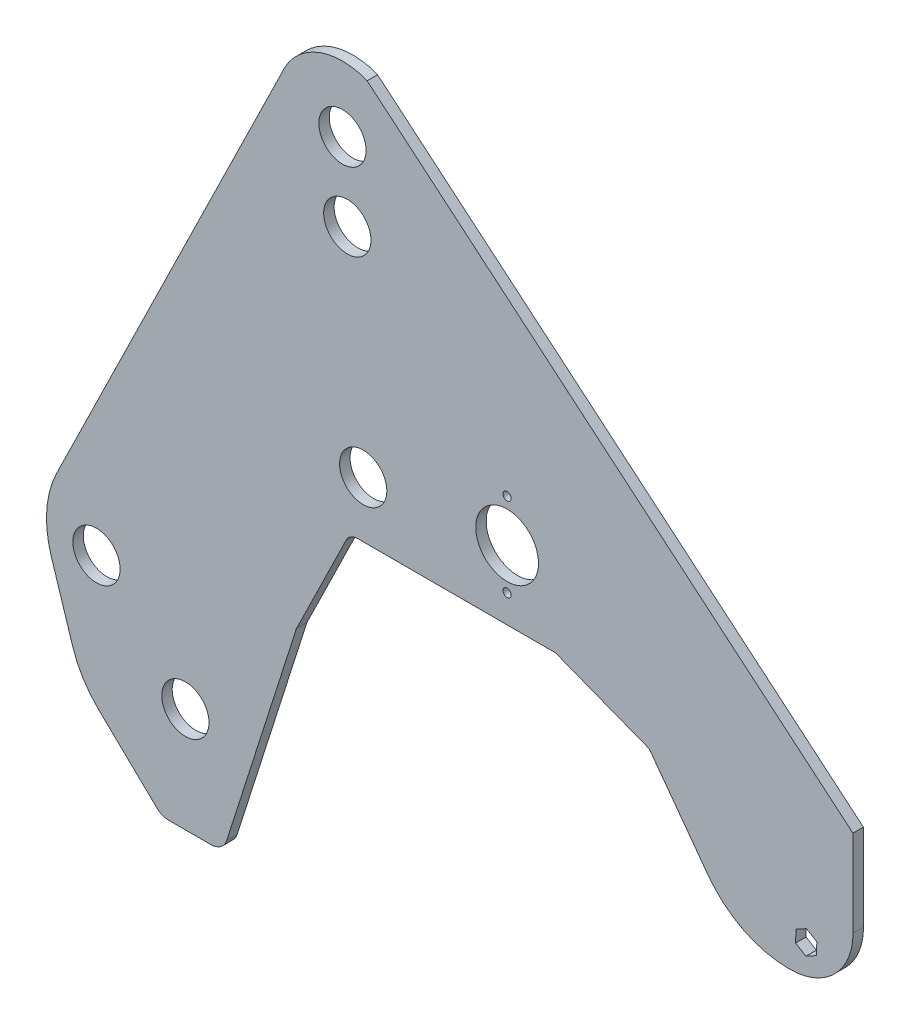
SolidWorks part; units mm, degrees
other "Markup1"
sketch "Sketch1" plane through (-441.7893, 331.8239, 6.35) normal (-0.0431, 0.0102, 0.999) x (0.9985, 0.0354, 0.0427)
ref_plane "Front Plane" through (0, 0, 0) normal (0, 0, 1) x (1, 0, 0)
ref_plane "Top Plane" through (0, 0, 0) normal (0, 1, 0) x (1, 0, 0)
ref_plane "Right Plane" through (0, 0, 0) normal (1, 0, 0) x (0, 0, -1)
sketch "Model" plane through (0, 0, 0) normal (0, 0, 1) x (1, 0, 0)
  line L0 (75.9485, 40.4103) -> (75.882, 92.9412)
  line L1 (-224.8827, 97.4651) -> (-104.7249, 97.4651)
  line L2 (-261.9342, 31.5683) -> (-231.7249, 93.1989)
  line L3 (-304.235, -100.9045) -> (-261.9342, 31.5683)
  line L4 (-271.0052, 318.922) -> (-407.4479, 40.5627)
  line L5 (-410.7965, -4.7638) -> (-397.7579, -45.7118)
  line L6 (-104.7249, 97.4651) -> (-47.7354, 75.4359)
  line L7 (-381.9218, -71.1596) -> (-346.5817, -105.1379)
  line L8 (-47.7354, 75.4359) -> (-12.1905, 27.105)
  line L10 (36.9184, 2.262) -> (37.8485, 2.262)
  line L11 (75.882, 92.9412) -> (-219.0215, 341.0133)
  line L12 (-339.5399, -107.974) -> (-313.9135, -107.974)
  line L13 (53.9476, 24.8456) -> (47.6751, 28.6428)
  line L14 (47.6751, 28.6428) -> (41.2504, 25.1092)
  line L15 (41.2504, 25.1092) -> (41.0982, 17.7784)
  line L16 (41.0982, 17.7784) -> (47.3707, 13.9813)
  line L17 (47.3707, 13.9813) -> (53.7955, 17.5149)
  line L18 (53.7955, 17.5149) -> (53.9476, 24.8456)
  arc A2 (-219.0215, 341.0133) -> (-271.0052, 318.922) centre (-234, 304.0517) ccw
  circle A3 centre (-134.0441, 114.3) radius 2.4892
  arc A6 (-224.8827, 97.4651) -> (-231.7249, 93.1989) centre (-224.8827, 89.8451) ccw
  circle A9 centre (-329.3491, -44.474) radius 14.351
  circle A10 centre (-383.3239, 9.3141) radius 14.351
  circle A12 centre (-221.4052, 131.3317) radius 14.351
  circle A15 centre (-134.0441, 139.2879) radius 19.05
  circle A21 centre (-134.0441, 165.1) radius 2.4892
  circle A22 centre (-231.0489, 258.3317) radius 14.351
  circle A23 centre (-234, 304.0517) radius 14.351
  circle A24 centre (47.5229, 21.312) radius 6.35 construction
  arc A25 (-339.5399, -107.974) -> (-346.5817, -105.1379) centre (-339.5399, -97.814) cw
  arc A26 (-304.235, -100.9045) -> (-313.9135, -107.974) centre (-313.9135, -97.814) cw
  arc A27 (75.9485, 40.4103) -> (37.8485, 2.262) centre (37.8485, 40.362) cw
  arc A28 (-12.1905, 27.105) -> (36.9184, 2.262) centre (36.9184, 63.222) ccw
  arc A29 (-410.7965, -4.7638) -> (-407.4479, 40.5627) centre (-352.7101, 13.732) cw
  arc A30 (-397.7579, -45.7118) -> (-381.9218, -71.1596) centre (-339.6715, -27.216) ccw
  dimension "D2" = 127
  dimension "D3" = 38.1
  dimension "D4" = 60.96
  dimension "D5" = 7.62
  dimension "D6" = 10.16
  dimension "D1" = 127
  dimension "D7" = 12.7
  dimension "D8" = 152.4
  dimension "D11" = 60.96
  dimension "D12" = 60.96
  dimension "D9" = 19.05
  dimension "D10" = 76.2
  dimension "D13" = 129.286
  dimension "D14" = 45.72
  dimension "D15" = 33.8667
  dimension "D16" = 63.5
  dimension "D17" = 291.886
  dimension "D18" = 206.2996
  dimension "D19" = 41.8228
  dimension "D20" = 134.62
extrude "Boss-Extrude1" add sketch "Model" along normal blind 6.35 contours L5 L7 L3 L2 L1 L6 L8 L10 L0 L11 A2 L4 A23 A22 A21 A3 A9 A10 A12 A15 region at (-201.4976, 125.4027, 0)
